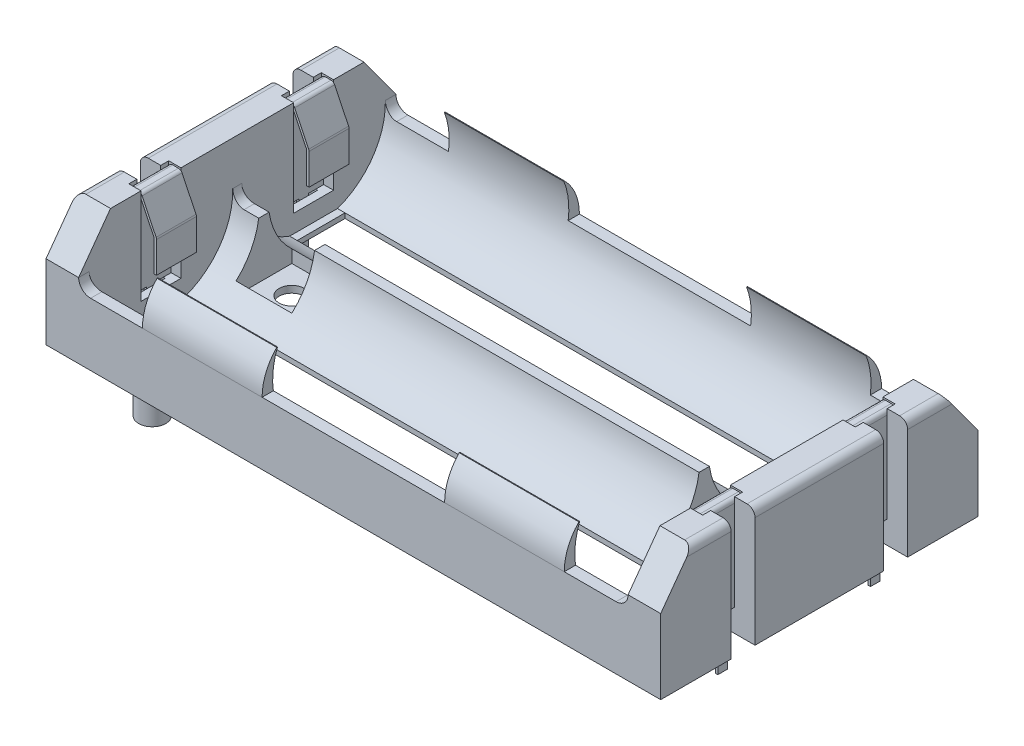
SolidWorks part; units mm, degrees
note: The reader was unsure of these and kept them because the rebuilt part matched: shared geometry of "Sketch6<2>", "Sketch8<2>".
ref_plane "Front Plane" through (0, 0, 0) normal (0, 0, 1) x (1, 0, 0)
ref_plane "Top Plane" through (0, 0, 0) normal (0, 1, 0) x (1, 0, 0)
ref_plane "Right Plane" through (0, 0, 0) normal (1, 0, 0) x (0, 0, -1)
sketch "Sketch1" plane through (0, 0, 0) normal (0, 0, 1) x (1, 0, 0)
  line L1 (-38.53, 0) -> (38.53, 0)
  line L2 (-38.53, 0) -> (-38.53, 14.85)
  line L3 (-38.53, 14.85) -> (38.53, 14.85)
  line L4 (38.53, 0) -> (38.53, 14.85)
  dimension "D1" = 77.06
  dimension "D2" = 14.85
extrude "Boss-Extrude1" add sketch "Sketch1" along normal blind 19.89
sketch "Sketch2" plane through (0, 0, 0) normal (1, 0, 0) x (0, 0, -1)
  line L0 (0, 0) -> (0, 14.85) construction
  line L2 (-19.89, 0) -> (0, 0) construction
  circle A0 centre (-9.565, 9.1) radius 9
  dimension "D1" = 18
  dimension "D2" = 9.565
  dimension "D3" = 9.1
extrude "Cut-Extrude2" cut sketch "Sketch2" against normal blind 34.44 and the other way blind 34.44 contours A0
sketch "Sketch3" plane through (0, 0, 19.89) normal (0, 0, 1) x (1, 0, 0)
  line L0 (-34.44, 14.85) -> (-34.44, 9.35)
  line L1 (38.53, 14.85) -> (-38.53, 14.85) construction
  line L2 (-32.94, 7.85) -> (-26.44, 7.85)
  line L3 (-26.44, 7.85) -> (-26.44, 12.35)
  line L4 (-26.44, 12.35) -> (-11.44, 12.35)
  line L5 (-11.44, 12.35) -> (-11.44, 7.85)
  line L6 (-11.44, 7.85) -> (11.44, 7.85)
  line L7 (0, 7.85) -> (0, 14.85) construction
  line L8 (34.44, 14.85) -> (-34.44, 14.85)
  line L9 (11.44, 12.35) -> (11.44, 7.85)
  line L10 (26.44, 12.35) -> (11.44, 12.35)
  line L11 (26.44, 7.85) -> (26.44, 12.35)
  line L12 (32.94, 7.85) -> (26.44, 7.85)
  line L13 (34.44, 14.85) -> (34.44, 9.35)
  arc A0 (32.94, 7.85) -> (34.44, 9.35) centre (32.94, 9.35) ccw
  arc A1 (-34.44, 9.35) -> (-32.94, 7.85) centre (-32.94, 9.35) ccw
  point P16 (-24.697, 11.1351)
  point P19 (34.44, 7.85)
  point P22 (-34.44, 7.85)
  dimension "D6" = 1.5
  dimension "D1" = 68.88
  dimension "D2" = 7
  dimension "D3" = 2.5
  dimension "D4" = 15
  dimension "D5" = 8
extrude "Cut-Extrude3" cut sketch "Sketch3" against normal through all
sketch "Sketch4" plane through (-26.44, 0, 0) normal (-1, 0, 0) x (0, 0, 1)
  line L4 (9.945, 14.85) -> (9.945, 0) construction
  line L5 (19.89, 14.85) -> (0, 14.85) construction
  line L6 (19.89, 0) -> (0, 0) construction
  line L7 (19.89, 7.85) -> (19.89, 0) construction
  line L8 (19.89, 12.35) -> (19.89, 7.85)
  line L9 (18.0577, 12.35) -> (19.89, 12.35)
  line L10 (19.89, 7.85) -> (19.89, 12.35) construction
  line L11 (18.4778, 7.85) -> (19.89, 7.85) construction
  arc A1 (19.89, 7.85) -> (18.0577, 12.35) centre (13.448, 7.85) ccw
  point P0 (19.89, 6.85)
  dimension "D1" = 0.1
extrude "Cut-Extrude4" cut sketch "Sketch4" against normal up to surface (52.88 mm away) contours A1 L9 L8 up to face at (26.44, 10.1083, 19.1258)
sketch "Sketch5" plane through (0, 0, 0) normal (0, 0, -1) x (-1, 0, 0)
  line L1 (-26.44, 12.35) -> (26.44, 12.35)
  line L2 (-26.44, 12.35) -> (-26.44, 7.85)
  line L3 (-26.44, 7.85) -> (26.44, 7.85)
  line L4 (26.44, 12.35) -> (26.44, 7.85)
extrude "Cut-Extrude5" cut sketch "Sketch5" against normal up to next
sketch "Sketch6" plane through (-38.53, 0, 0) normal (-1, 0, 0) x (0, 0, 1)
  line L0 (19.89, 9.35) -> (15.89, 14.85)
  line L1 (19.89, 14.85) -> (0, 14.85) construction
  line L2 (15.89, 14.85) -> (19.89, 14.85)
  line L3 (19.89, 14.85) -> (19.89, 9.35)
  dimension "D1" = 4
extrude "Cut-Extrude6" cut sketch "Sketch6" against normal up to next
extrude "Cut-Extrude7" cut sketch "Sketch6<2>" against normal through all from surface at -72.97 starting at face at (34.44, 9.6417, 9.8183)
sketch "Sketch6<2>" plane through (-38.53, 0, 0) normal (-1, 0, 0) x (0, 0, 1) same geometry as "Sketch6"
sketch "Sketch7" plane through (0, 14.85, 0) normal (0, 1, 0) x (1, 0, 0)
  line L0 (-34.44, -9.565) -> (-33.5, -9.565) construction
  line L1 (-33.5, -6.565) -> (33.5, -6.565)
  line L2 (-33.5, -6.565) -> (-33.5, -12.565)
  line L3 (-33.5, -12.565) -> (33.5, -12.565)
  line L4 (33.5, -6.565) -> (33.5, -12.565)
  line L5 (-34.44, -18.565) -> (-34.44, -0.565) construction
  line L6 (0, 0) -> (0, -6.565) construction
  dimension "D1" = 67
  dimension "D2" = 6
extrude "Cut-Extrude8" cut sketch "Sketch7" against normal through all
sketch "Sketch8" plane through (-33.5, 0, 0) normal (1, 0, 0) x (0, 0, -1)
  line L1 (-12.565, 0) -> (-6.565, 0)
  line L2 (-12.565, 0) -> (-12.565, 0.6147)
  line L3 (-12.565, 0.6147) -> (-6.565, 0.6147)
  line L4 (-6.565, 0) -> (-6.565, 0.6147)
extrude "Boss-Extrude2" add sketch "Sketch8" against normal up to surface (0.94 mm away) up to face at (-34.44, 9.6417, 9.1517)
extrude "Boss-Extrude3" add sketch "Sketch8<2>" along normal up to surface (0.94 mm away) from surface at 67 up to face at (34.44, 9.6417, 9.1517) starting at face at (33.5, 0.1787, 9.565)
sketch "Sketch8<2>" plane through (-33.5, 0, 0) normal (1, 0, 0) x (0, 0, -1) same geometry as "Sketch8"
fillet "Fillet1" radius 1 2 edges at (-38.53, 14.85, 7.945) (38.53, 14.85, 7.945)
sketch "Sketch9" plane through (0, 14.85, 0) normal (0, 1, 0) x (1, 0, 0)
  line L0 (38.53, 0) -> (38.53, -16.6173) construction
  line L1 (35.44, -8.065) -> (38.53, -8.065)
  line L2 (35.44, -8.065) -> (35.44, -11.065)
  line L3 (35.44, -11.065) -> (38.53, -11.065)
  line L4 (38.53, -8.065) -> (38.53, -11.065)
  line L7 (35.44, -9.565) -> (34.44, -9.565) construction
  line L8 (34.44, -12.565) -> (34.44, -6.565) construction
  point P9 (0, 0)
  point P14 (0, 0)
  dimension "D1" = 1
  dimension "D2" = 3
extrude "Cut-Extrude9" cut sketch "Sketch9" against normal through all
mirror "Mirror1" about plane through (0, 0, 0) normal (1, 0, 0) of "Cut-Extrude9"
sketch "Sketch10" plane through (0, 14.85, 0) normal (0, 1, 0) x (1, 0, 0)
  line L0 (34.44, -0.565) -> (34.44, -6.565) construction
  line L1 (34.44, -7.065) -> (35.97, -7.065)
  line L2 (34.44, -7.065) -> (34.44, -12.065)
  line L3 (34.44, -12.065) -> (35.97, -12.065)
  line L4 (35.97, -7.065) -> (35.97, -12.065)
  line L7 (35.44, -9.565) -> (35.97, -9.565) construction
  line L8 (35.44, -8.065) -> (35.44, -11.065) construction
  dimension "D1" = 5
  dimension "D2" = 35.97
extrude "Cut-Extrude10" cut sketch "Sketch10" against normal blind 12
mirror "Mirror2" about plane through (0, 0, 0) normal (1, 0, 0) of "Cut-Extrude10"
sketch "Sketch11" plane through (0, 0, 7.065) normal (0, 0, 1) x (1, 0, 0)
  line L0 (32.5, 6.65) -> (32.5, 10.5351)
  line L1 (32.5501, 10.7533) -> (34.3033, 14.3682)
  line L2 (34.7532, 14.65) -> (35.47, 14.65)
  line L3 (35.97, 14.15) -> (35.97, 2.85)
  line L4 (35.97, 2.85) -> (35.97, 14.85) construction
  line L5 (35.97, 14.85) -> (34.44, 14.85) construction
  line L6 (34.44, 2.85) -> (34.44, 14.85) construction
  arc A0 (35.47, 14.65) -> (35.97, 14.15) centre (35.47, 14.15) cw
  arc A1 (34.3033, 14.3682) -> (34.7532, 14.65) centre (34.7532, 14.15) cw
  arc A2 (32.5, 10.5351) -> (32.5501, 10.7533) centre (33, 10.5351) cw
  point P10 (0, 0)
  point P17 (34.44, 14.65)
  point P20 (32.5, 10.65)
  point P21 (0, 0)
  dimension "D5" = 0.5
  dimension "D1" = 32.5
  dimension "D2" = 0.2
  dimension "D3" = 4
  dimension "D4" = 4
extrude "Extrude-Thin1" add sketch "Sketch11" along normal up to surface (5 mm away) separate body thin
sketch "Sketch12" plane through (35.97, 0, 0) normal (1, 0, 0) x (0, 0, -1)
  line L0 (-11.065, 2.85) -> (-8.065, 2.85) construction
  line L1 (-10.165, 2.85) -> (-8.965, 2.85)
  line L2 (-10.165, 2.85) -> (-10.165, -3.43)
  line L3 (-10.165, -3.43) -> (-8.965, -3.43)
  line L4 (-8.965, 2.85) -> (-8.965, -3.43)
  line L5 (-8.065, 0) -> (0, 0) construction
  point P6 (-10.0022, 2.85)
  point P7 (-9.565, 2.85)
  point P8 (-9.565, 2.85)
  dimension "D1" = 1.2
  dimension "D2" = 3.43
extrude "Boss-Extrude4" add sketch "Sketch12" against normal blind 0.3
mirror "Mirror3" about plane through (0, 0, 0) normal (1, 0, 0) of bodies 116
mirror "Mirror4" about plane through (0, 0, 0) normal (0, 0, 1) of bodies 114
mirror "Mirror5" about plane through (0, 0, 0) normal (0, 0, 1) of bodies 116 117
sketch "Sketch13" plane through (0, 7.85, 0) normal (0, 1, 0) x (1, 0, 0)
  line L0 (-27.6, 0) -> (0, 0) construction
  line L1 (-31.1, -3.5) -> (-24.1, -3.5)
  line L2 (-31.1, -3.5) -> (-31.1, 3.5)
  line L3 (-31.1, 3.5) -> (-24.1, 3.5)
  line L4 (-24.1, -3.5) -> (-24.1, 3.5)
  line L5 (-31.1, -3.5) -> (-24.1, 3.5) construction
  line L6 (-31.1, 3.5) -> (-24.1, -3.5) construction
  point P0 (-27.6, 0)
  dimension "D1" = 27.6
  dimension "D2" = 7
extrude "Cut-Extrude11" cut sketch "Sketch13" against normal blind 7
sketch "Sketch14" plane through (0, 0.85, 0) normal (0, 1, 0) x (1, 0, 0)
  line L0 (-31.1, 3.5) -> (-24.1, -3.5) construction
  circle A0 centre (-27.6, 0) radius 1.59
  point P6 (0, 0)
  dimension "D1" = 3.18
extrude "Cut-Extrude12" cut sketch "Sketch14" against normal through all
mirror "Mirror6" about plane through (0, 0, 0) normal (1, 0, 0) of "Cut-Extrude12", "Cut-Extrude11"
sketch "Sketch15" plane through (0, 0, 0) normal (0, -1, 0) x (1, 0, 0)
  line L0 (-27.6, 0) -> (-27.6, 17.5) construction
  line L1 (27.6, 0) -> (27.6, -17.5) construction
  circle A0 centre (-27.6, 17.5) radius 1.7
  circle A1 centre (27.6, -17.5) radius 1.7
  dimension "D1" = 3.4
  dimension "D2" = 3.4
  dimension "D3" = 17.5
  dimension "D4" = 17.5
extrude "Boss-Extrude5" add sketch "Sketch15" along normal through all
equation "\"D1@Sketch11\"=65/2"
equation "\"D2@Sketch10\"=71.64/2+0.3/2"
equation "\"D4@Sketch15\"=\"D3@Sketch15\""
